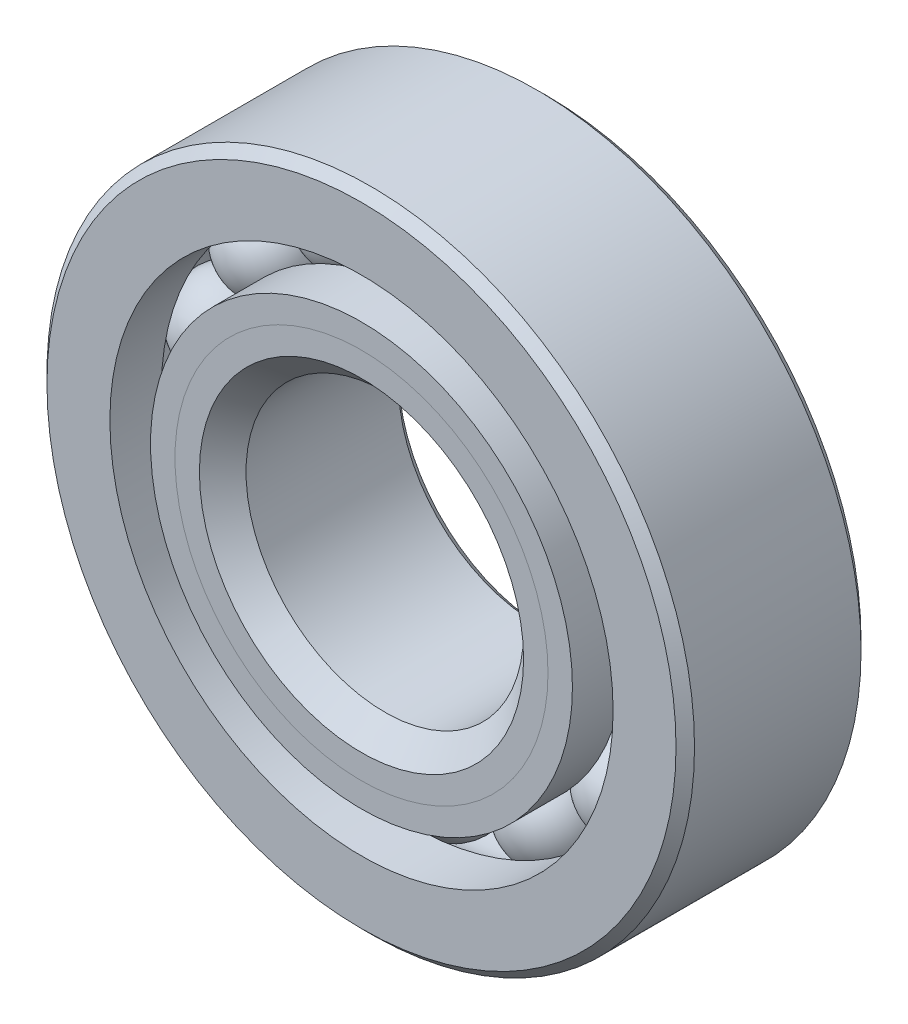
SolidWorks part; units mm, degrees
ref_plane "Front Plane" through (0, 0, 0) normal (0, 0, 1) x (1, 0, 0)
ref_plane "Top Plane" through (0, 0, 0) normal (0, 1, 0) x (1, 0, 0)
ref_plane "Right Plane" through (0, 0, 0) normal (1, 0, 0) x (0, 0, -1)
sketch "Sketch1" plane through (0, 0, 0) normal (1, 0, 0) x (0, 0, -1)
  line L0 (-3.175, 0) -> (3.175, 0) construction
  line L1 (0, 11.1125) -> (0, -11.1125) construction
  line L2 (2.8575, 11.1125) -> (-2.8575, 11.1125)
  line L3 (-2.8575, 11.1125) -> (-3.175, 10.795)
  line L4 (-3.175, 10.795) -> (-3.175, 8.6353)
  line L5 (-3.175, 8.6353) -> (-1.4111, 8.6353)
  line L6 (3.175, 8.6353) -> (1.4111, 8.6353)
  line L7 (3.175, 10.795) -> (3.175, 8.6353)
  line L8 (2.8575, 11.1125) -> (3.175, 10.795)
  line L9 (0, 11.1125) -> (0, 7.9375) construction
  line L10 (0, 7.9375) -> (0, 4.7625) construction
  arc A0 (-1.4111, 8.6353) -> (1.4111, 8.6353) centre (0, 7.9375) cw
  point P14 (0, 4.7625)
  dimension "D3" = 2.8222
  dimension "D1" = 45
  dimension "Width" = 6.35
  dimension "OD" = 22.225
  dimension "D2" = 0.3175
  dimension "Shaft Dia" = 9.525
  dimension "D4" = 0.6978
revolve "Revolve1" add sketch "Sketch1" angle 360 about L0
sketch "Sketch2" plane through (0, 0, 0) normal (1, 0, 0) x (0, 0, -1)
  line L0 (-3.175, 7.2397) -> (-1.4111, 7.2397)
  line L1 (-3.175, 10.795) -> (-3.175, -10.795) construction
  line L2 (-3.175, 7.2397) -> (-3.175, 6.4013)
  line L3 (-3.175, 6.4013) -> (-2.3366, 5.5629)
  line L4 (-2.3366, 5.5629) -> (0, 5.5629)
  line L5 (0, 11.1125) -> (0, -11.1125) construction
  line L6 (0, 5.5629) -> (0, 6.3633)
  line L7 (0, 6.3633) -> (0, 4.7625) construction
  line L8 (-3.175, 7.2397) -> (-3.175, 5.5629) construction
  line L9 (-3.175, 5.5629) -> (-2.3366, 5.5629) construction
  arc A0 (-1.4111, 7.2397) -> (0, 6.3633) centre (0, 7.9375) ccw
  arc A1 (1.4111, 8.6353) -> (-1.4111, 8.6353) centre (0, 7.9375) ccw construction
  circle A2 centre (0, 7.9375) radius 1.5742 construction
  dimension "D1" = 45
revolve "Revolve2" add sketch "Sketch2" angle 360 about L0
sketch "Sketch3" plane through (0, 0, 0) normal (1, 0, 0) x (0, 0, -1)
  line L0 (-3.175, 6.4013) -> (-2.3366, 5.5629)
  line L1 (-2.3366, 5.5629) -> (0, 5.5629)
  line L2 (0, 5.5629) -> (0, 6.3633)
  line L3 (-3.175, 6.4013) -> (-3.175, 5.5629)
  line L4 (-3.175, 7.2397) -> (-3.175, 5.5629) construction
  line L5 (-3.175, 5.5629) -> (-2.3746, 4.7625)
  line L6 (-2.3746, 4.7625) -> (2.8575, 4.7625)
  line L7 (2.8575, 11.1125) -> (2.8575, -11.1125) construction
  line L8 (2.8575, 4.7625) -> (3.175, 5.08)
  line L9 (3.175, -10.795) -> (3.175, 10.795) construction
  line L10 (3.175, 5.08) -> (3.175, 7.2397)
  line L11 (3.175, 7.2397) -> (1.4111, 7.2397)
  line L13 (2.8575, 11.1125) -> (3.175, 10.795) construction
  circle A0 centre (0, 7.9375) radius 1.5742 construction
  arc A1 (1.4111, 7.2397) -> (0, 6.3633) centre (0, 7.9375) cw
revolve "Revolve3" add sketch "Sketch3" angle 360 about L0
sketch "Sketch4" plane through (0, 0, 0) normal (1, 0, 0) x (0, 0, -1)
  line L0 (-1.5742, 7.9375) -> (1.5742, 7.9375)
  circle A1 centre (0, 7.9375) radius 1.5742 construction
  arc A2 (-1.5742, 7.9375) -> (1.5742, 7.9375) centre (0, 7.9375) cw
  arc A3 (1.4111, 8.6353) -> (-1.4111, 8.6353) centre (0, 7.9375) ccw construction
revolve "Revolve4" add sketch "Sketch4" angle 360 about L0
ref_axis "Axis1" through (0, 0, -3.175) along (0, 0, 1)
pattern_circular "CirPattern1" count 14 every 25.714 about axis through (0, 0, -3.175) along (0, 0, 1) of bodies 104
equation "\"D2@Sketch1\" = \"Width@Sketch1\"*.05"
equation "\"D3@Sketch1\" = \"Width@Sketch1\"/2.25"
equation "\"D4@Sketch1\" = (((\"OD@Sketch1\"-\"Width@Sketch1\")/2)/3.25)/3.5"
equation "\"D2@CirPattern1\" = 360/\"Balls@CirPattern1\""
